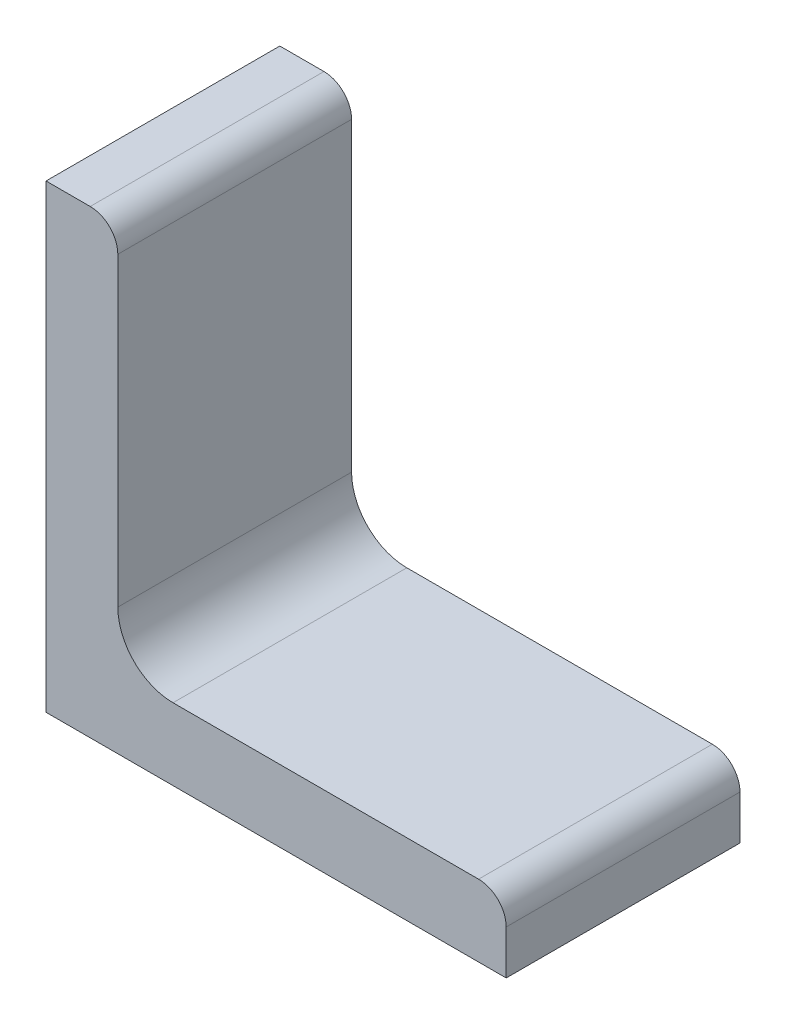
SolidWorks part; units mm, degrees
ref_plane "Front Plane" through (0, 0, 0) normal (0, 0, 1) x (1, 0, 0)
ref_plane "Top Plane" through (0, 0, 0) normal (0, 1, 0) x (1, 0, 0)
ref_plane "Right Plane" through (0, 0, 0) normal (1, 0, 0) x (0, 0, -1)
sketch "Sketch1" plane through (0, 0, 0) normal (0, 0, 1) x (1, 0, 0)
  line L1 (0, 0) -> (50, 0)
  line L2 (0, 0) -> (0, 50)
  line L3 (0, 50) -> (4.8, 50)
  line L4 (50, 0) -> (50, 4.8)
  line L6 (7.8, 47) -> (7.8, 13.8)
  line L7 (13.8, 7.8) -> (47, 7.8)
  arc A0 (7.8, 13.8) -> (13.8, 7.8) centre (13.8, 13.8) ccw
  arc A1 (4.8, 50) -> (7.8, 47) centre (4.8, 47) cw
  arc A2 (50, 4.8) -> (47, 7.8) centre (47, 4.8) ccw
  dimension "Radius_root" = 6
  dimension "Radius_toe" = 3
  dimension "Width" = 50
  dimension "Thickness" = 7.8
extrude "BaseSection" add sketch "Sketch1" along normal mid plane 25.4
